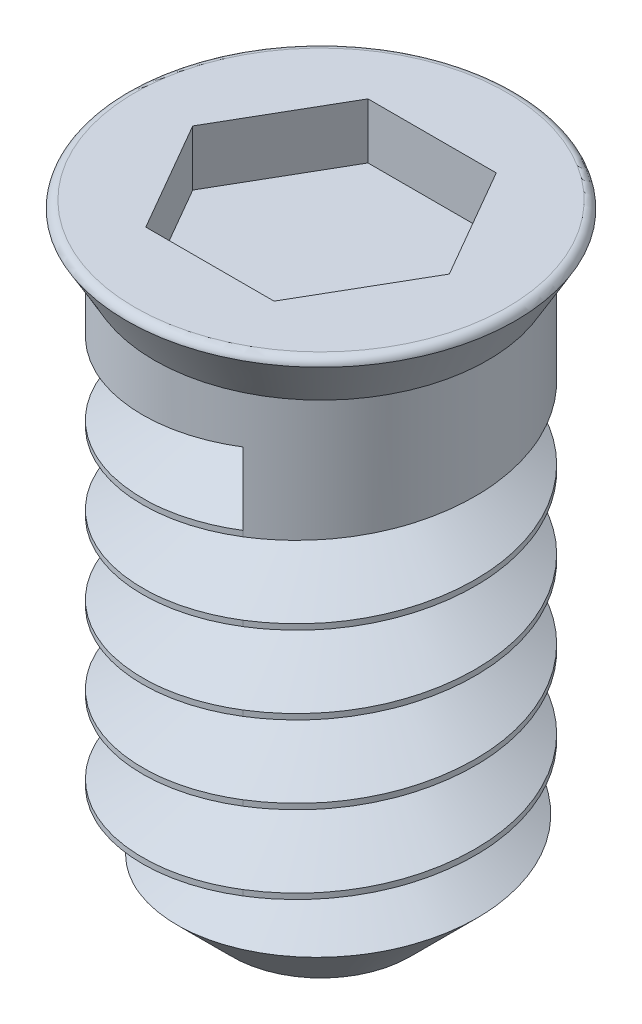
SolidWorks part; units mm, degrees
ref_plane "Front Plane" through (0, 0, 0) normal (0, 0, 1) x (1, 0, 0)
ref_plane "Top Plane" through (0, 0, 0) normal (0, 1, 0) x (1, 0, 0)
ref_plane "Right Plane" through (0, 0, 0) normal (1, 0, 0) x (0, 0, -1)
sketch "Sketch1" plane through (0, 0, 0) normal (0, 1, 0) x (1, 0, 0)
  circle A0 centre (0, 0) radius 3.5
  dimension "D1" = 7
extrude "Boss-Extrude2" add sketch "Sketch1" along normal blind 2
sketch "Sketch2" plane through (0, 2, 0) normal (0, 1, 0) x (1, 0, 0)
  line L1 (2.3094, 0) -> (1.1547, 2)
  line L2 (1.1547, 2) -> (-1.1547, 2)
  line L3 (-1.1547, 2) -> (-2.3094, 0)
  line L4 (-2.3094, 0) -> (-1.1547, -2)
  line L5 (-1.1547, -2) -> (1.1547, -2)
  line L6 (1.1547, -2) -> (2.3094, 0)
  circle A0 centre (0, 0) radius 2 construction
  dimension "D1" = 4
extrude "Cut-Extrude1" cut sketch "Sketch2" against normal blind 1.5
fillet "Fillet2" radius 0.15 1 edges at (0, 2, 3.5)
sketch "Sketch3" plane through (0, 0, 0) normal (0, -1, 0) x (1, 0, 0)
  circle A0 centre (0, 0) radius 2.5
  circle A1 centre (0, 0) radius 3.5
extrude "Cut-Extrude4" cut sketch "Sketch3" against normal blind 1
sketch "Sketch4" plane through (0, 1, 0) normal (0, -1, 0) x (1, 0, 0)
  circle A1 centre (0, 0) radius 3
extrude "Cut-Extrude8" cut sketch "Sketch4" against normal blind 10 draft 30 flip side to cut
sketch "Sketch5" plane through (0, 1, 0) normal (0, -1, 0) x (1, 0, 0)
  circle A0 centre (0, 0) radius 3
extrude "Boss-Extrude3" add sketch "Sketch5" along normal blind 10
chamfer "Chamfer1" distance 1.4 angle 45 1 edges at (0, -9, -3)
sketch "Sketch6" plane through (0, -9, 0) normal (0, -1, 0) x (1, 0, 0)
  circle A0 centre (0, 0) radius 3 construction
  circle A1 centre (0, 0) radius 3
curve "Helix/Spiral2" pitch 1.4 height 8.5 radius 3 centre (0, -9, 0) axis (0, 1, 0) start towards (0, 0, 1)
sketch "Sketch8" plane through (0, 0, 0) normal (0, 0, 1) x (1, 0, 0)
  line L0 (3, -1) -> (3, -2.3)
  line L1 (3, -2.3) -> (2, -1.7)
  line L2 (2, -1.7) -> (2, -1.6)
  line L3 (2, -1.6) -> (3, -1)
  point P2 (2, -1.65)
  point P5 (3, -1.65)
  dimension "D1" = 1
  dimension "D2" = 1.3
  dimension "D3" = 0.1
sweep "Cut-Sweep4" cut profiles "Sketch8" path "Helix/Spiral2" align with end faces yes
